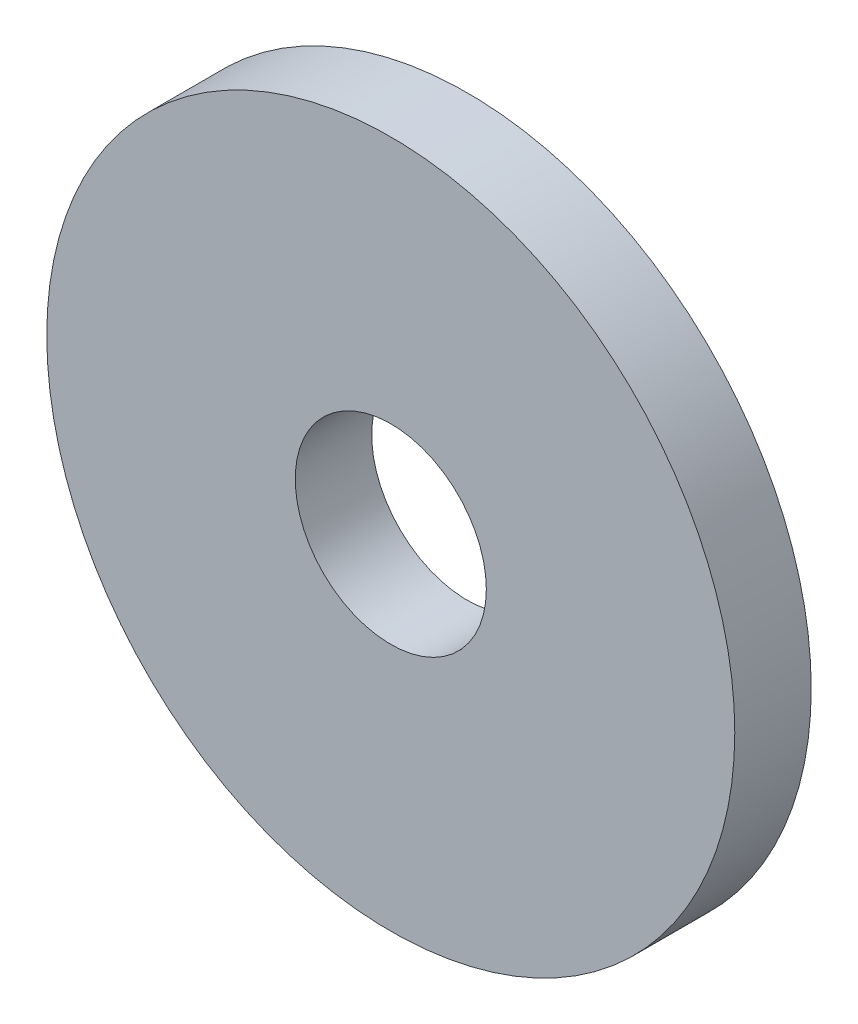
SolidWorks part; units mm, degrees
ref_plane "Front" through (0, 0, 0) normal (0, 0, 1) x (1, 0, 0)
ref_plane "Top" through (0, 0, 0) normal (0, 1, 0) x (1, 0, 0)
ref_plane "Right" through (0, 0, 0) normal (1, 0, 0) x (0, 0, -1)
sketch "Sketch1" plane through (0, 0, 0) normal (0, 0, 1) x (1, 0, 0)
  circle A0 centre (0, 0) radius 2.5
  circle A1 centre (0, 0) radius 9
  dimension "d1" = 5
  dimension "d2" = 18
extrude "Base-Extrude" add sketch "Sketch1" against normal blind 2
